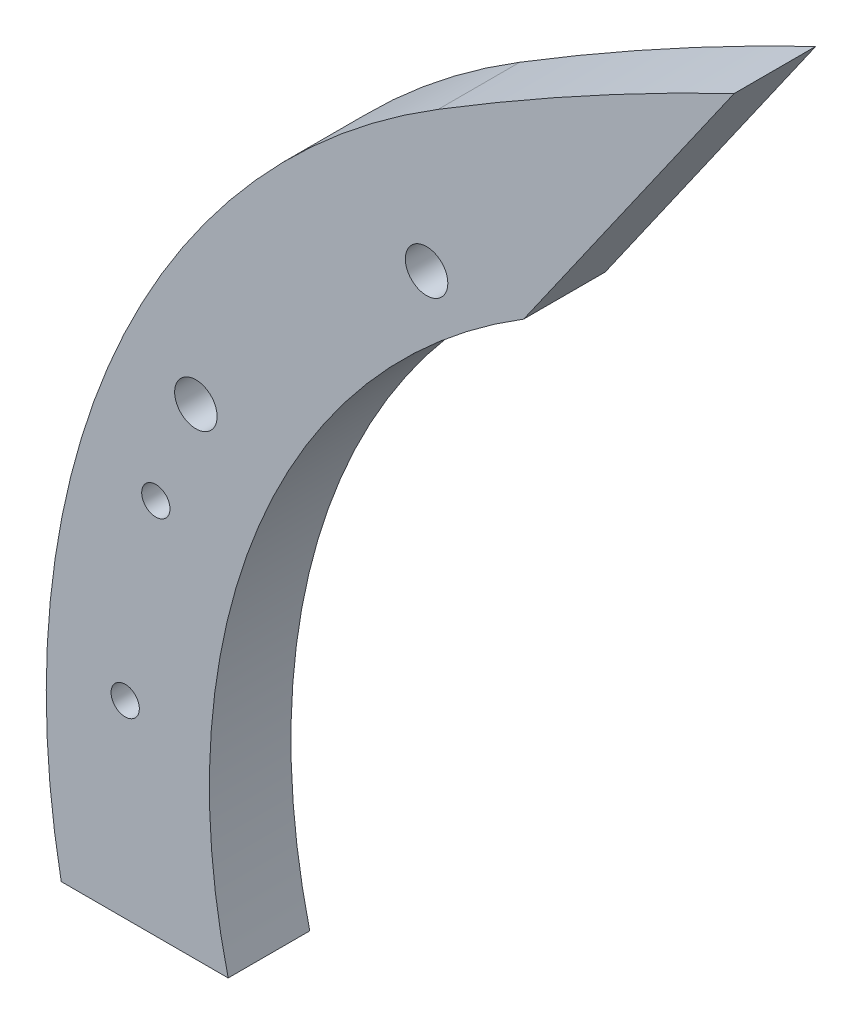
SolidWorks part; units mm, degrees
ref_plane "Front Plane" through (0, 0, 0) normal (0, 0, 1) x (1, 0, 0)
ref_plane "Top Plane" through (0, 0, 0) normal (0, 1, 0) x (1, 0, 0)
ref_plane "Right Plane" through (0, 0, 0) normal (1, 0, 0) x (0, 0, -1)
sketch "Sketch1" plane through (0, 0, 0) normal (0, 0, 1) x (1, 0, 0)
  line L0 (-80.6589, 131.2575) -> (-31.489, 201.4793)
  line L1 (-149.6704, -36.5125) -> (-188.6589, -36.5125)
  line L2 (0, -36.5125) -> (-306.0798, -36.5125) construction
  circle A0 centre (0, 0) radius 36.5125 construction
  arc A1 (-80.6589, 131.2575) -> (-149.6704, -36.5125) centre (0, 0) ccw
  arc A2 (-100.6064, 163.7183) -> (-188.6589, -36.5125) centre (0, 0) ccw
  arc A3 (-100.6064, 163.7183) -> (-31.489, 201.4793) centre (303.8551, -494.4683) cw
  dimension "D1" = 73.025
  dimension "D3" = 38.1
  dimension "D4" = 772.5275
  dimension "D5" = 303.8551
  dimension "D2" = 154.0597
  dimension "D6" = 36.5125
  dimension "D7" = 125
  dimension "D9" = 85.725
extrude "Boss-Extrude1" add sketch "Sketch1" along normal mid plane 19.05
ref_axis "Axis1" through (0, 0, 0) along (0, 0, 1)
sketch "Sketch2" plane through (0, 0, 9.525) normal (0, 0, 1) x (1, 0, 0)
  circle A0 centre (-173.7187, 7.5796) radius 3.302 construction
  circle A1 centre (-166.5648, 51.5693) radius 3.302 construction
  circle A2 centre (-173.7187, 7.5796) radius 3.302
  circle A3 centre (-166.5648, 51.5693) radius 3.302
extrude "Cut-Extrude1" cut sketch "Sketch2" against normal up to surface (19.05 mm away) up to face at (-122.0294, 89.8594, -9.525)
hole_wizard "25/64 (0.39063) Diameter Hole1" positions "Sketch3" profile "Sketch4" hole size "25/64" standard "ANSI Inch" end condition through all
sketch "Sketch3" plane through (0, 0, 9.525) normal (0, 0, 1) x (1, 0, 0)
  line L0 (-31.489, 201.4793) -> (-157.2126, 75.7557) construction
  line L3 (-80.6589, 131.2575) -> (-31.489, 201.4793) construction
  point P0 (-103.3311, 129.6372)
  point P2 (-157.2126, 75.7557)
  point P10 (-102.5878, 121.5199)
  point P15 (-93.6436, 128.7555)
  point P16 (0, 0)
  dimension "D1" = 76.2
  dimension "D2" = 101.6
  dimension "D3" = 10
sketch "Sketch4" plane through (-103.3311, 129.6372, 9.525) normal (1, 0, 0) x (0, -1, 0)
  line L0 (0, 0) -> (0, 19.05)
  line L1 (0, 19.05) -> (4.961, 19.05)
  line L2 (4.961, 19.05) -> (4.961, 0)
  line L5 (4.961, 0) -> (0, 0)
  line L11 (0, -6.35) -> (0, 107.95) construction
  dimension "Thru Hole Dia." = 9.922
  dimension "Thru Hole Depth" = 19.05
